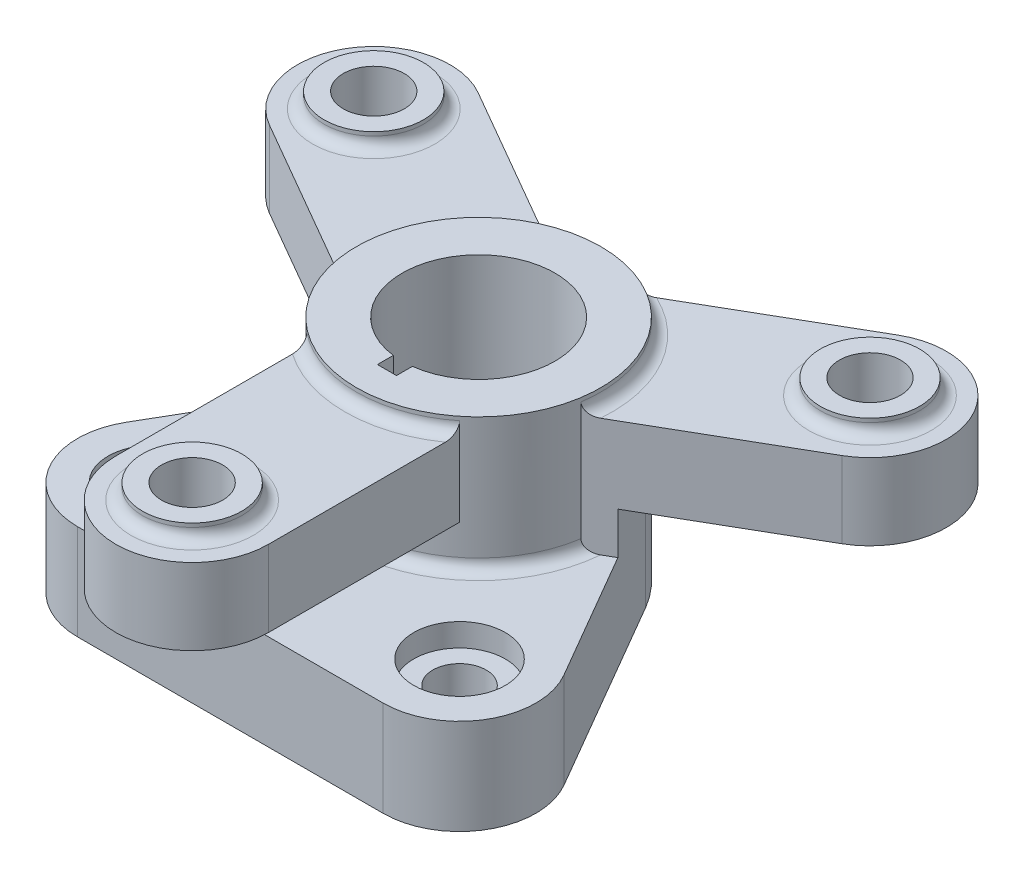
SolidWorks part; units mm, degrees
ref_plane "Front Plane" through (0, 0, 0) normal (0, 0, 1) x (1, 0, 0)
ref_plane "Top Plane" through (0, 0, 0) normal (0, 1, 0) x (1, 0, 0)
ref_plane "Right Plane" through (0, 0, 0) normal (1, 0, 0) x (0, 0, -1)
sketch "Sketch1" plane through (0, 0, 0) normal (0, 1, 0) x (1, 0, 0)
  line L0 (-75, 0) -> (75, 0) construction
  line L1 (0, -75) -> (0, 75) construction
  line L2 (0, 0) -> (64.9519, 37.5) construction
  line L3 (31.6333, -4.8305) -> (74.9519, 20.1795)
  line L4 (11.6333, 29.8105) -> (54.9519, 54.8205)
  line L5 (20, -24.98) -> (20, -75)
  line L6 (-20, -24.98) -> (-20, -75)
  line L7 (0, 0) -> (0, -75) construction
  line L8 (-31.6333, -4.8305) -> (-74.9519, 20.1795)
  line L9 (-11.6333, 29.8105) -> (-54.9519, 54.8205)
  line L10 (0, 0) -> (-64.9519, 37.5) construction
  line L11 (-2.5, -24) -> (2.5, -24)
  line L12 (-2.5, -24) -> (-2.5, -19.8431)
  line L13 (2.5, -24) -> (2.5, -19.8431)
  line L14 (-57.2966, -34.9586) -> (-27.6745, 16.0662)
  line L15 (-40, -65) -> (-20, -65)
  line L16 (40, -65) -> (20, -65)
  line L17 (57.2966, -34.9586) -> (27.6745, 16.0662)
  line L18 (-20, -65) -> (20, -65)
  arc A0 (2.5, -19.8431) -> (-2.5, -19.8431) centre (0, 0) ccw
  circle A1 centre (0, 0) radius 32
  circle A2 centre (0, 0) radius 75 construction
  circle A3 centre (64.9519, 37.5) radius 8
  circle A4 centre (64.9519, 37.5) radius 13
  arc A5 (74.9519, 20.1795) -> (54.9519, 54.8205) centre (64.9519, 37.5) ccw
  arc A6 (-20, -75) -> (20, -75) centre (0, -75) ccw
  circle A7 centre (0, -75) radius 13
  circle A8 centre (0, -75) radius 8
  arc A9 (-54.9519, 54.8205) -> (-74.9519, 20.1795) centre (-64.9519, 37.5) ccw
  circle A10 centre (-64.9519, 37.5) radius 13
  circle A11 centre (-64.9519, 37.5) radius 8
  circle A12 centre (-40, -45) radius 7
  circle A13 centre (-40, -45) radius 12
  circle A14 centre (40, -45) radius 7
  circle A15 centre (40, -45) radius 12
  arc A16 (-57.2966, -34.9586) -> (-40, -65) centre (-40, -45) ccw
  arc A17 (40, -65) -> (57.2966, -34.9586) centre (40, -45) ccw
  point P11 (0, 0)
  point P34 (0, 0)
  dimension "D1" = 40
  dimension "D2" = 64
  dimension "D5" = 150
  dimension "D6" = 26
  dimension "D7" = 16
  dimension "D8" = 40
  dimension "D12" = 24
  dimension "D13" = 14
  dimension "D16" = 40
  dimension "D3" = 150
  dimension "D4" = 30
  dimension "D9" = 3
  dimension "D10" = 5
  dimension "D11" = 24
  dimension "D14" = 45
  dimension "D15" = 40
extrude "Boss-Extrude4" add sketch "Sketch1" against normal blind 25 contours L14 A16 L15 L6 A1 L8 A13 | L16 A17 L17 L3 A1 L5 A15 | A7 L18 L5 A1 L6 | L18 A7 | A1 L14 L8 | A1 L3 L17 | A13 A12 | A15 A14 region at (33.497, 0, -1.9068) region at (35.0699, 0, 3.715) region at (0, 0, 46.9189) region at (-20.7522, 0, 44.99) region at (0, 0, 63.7873) region at (-33.497, 0, -1.9068) region at (-51.6606, 0, 45) region at (28.3394, 0, 45)
extrude "Boss-Extrude5" add sketch "Sketch1<8>" along normal blind 20 from offset 11 separate body contours A7 L18 L5 A1 L6 | A7 L18 L6 A6 L5 | L3 A5 L4 A1 L17 A4 | L9 A9 L8 L14 A1 A10 region at (49.122, 0, -28.7821) region at (0, 0, 46.9189) region at (19.5, 0, 70) region at (-49.122, 0, -28.7821)
sketch "Sketch1<8>" plane through (0, 0, 0) normal (0, 1, 0) x (1, 0, 0) same geometry as "Sketch1"
extrude "Boss-Extrude6" add sketch "Sketch1<9>" along normal blind 24 from offset 11 contours L18 A7 A8 | A4 A3 | A10 A11 | L18 A7 region at (11.4541, 0, 69.6242) region at (0, 0, 63.7873) region at (52.3196, 0, -37.5) region at (-77.5842, 0, -37.5)
sketch "Sketch1<9>" plane through (0, 0, 0) normal (0, 1, 0) x (1, 0, 0) same geometry as "Sketch1"
extrude "Boss-Extrude7" add sketch "Sketch1<10>" along normal blind 35 and the other way through all contours A1 A0 L13 L11 L12 region at (26.929, 0, 15.5475)
sketch "Sketch1<10>" plane through (0, 0, 0) normal (0, 1, 0) x (1, 0, 0) same geometry as "Sketch1"
sketch "Sketch2" plane through (0, 0, 0) normal (0, 1, 0) x (1, 0, 0)
  circle A0 centre (40, -45) radius 12
  circle A1 centre (-40, -45) radius 12
  dimension "D1" = 24
extrude "Cut-Extrude1" cut sketch "Sketch2" against normal blind 6
extrude "Boss-Extrude8" add sketch "Sketch1<11>" along normal blind 31 contours A1 L14 L8 | A1 L3 L17 region at (33.497, 0, -1.9068) region at (-33.497, 0, -1.9068)
sketch "Sketch1<11>" plane through (0, 0, 0) normal (0, 1, 0) x (1, 0, 0) same geometry as "Sketch1"
fillet "Fillet2" radius 3 7 edges at (0, 0, 32) (-64.9519, 31, -24.5) (64.9519, 31, -24.5) (0, 31, 88) (-27.7128, 31, -16) (27.7128, 31, -16) (0, 31, 32)
